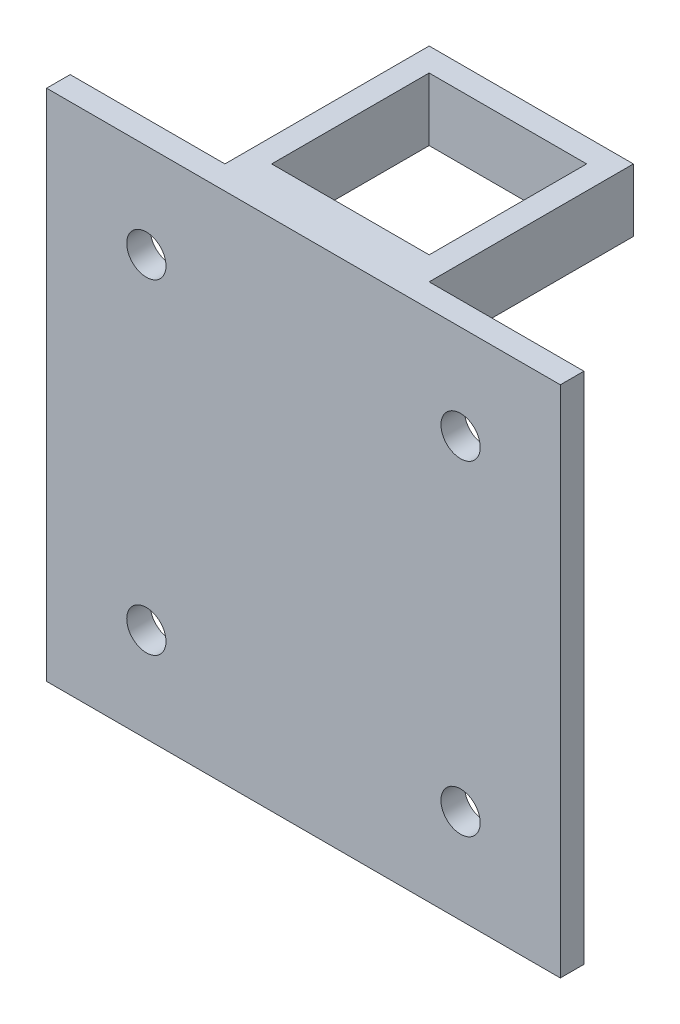
SolidWorks part; units mm, degrees
ref_plane "Спереди" through (0, 0, 0) normal (0, 0, 1) x (1, 0, 0)
ref_plane "Сверху" through (0, 0, 0) normal (0, 1, 0) x (1, 0, 0)
ref_plane "Справа" through (0, 0, 0) normal (1, 0, 0) x (0, 0, -1)
sketch "Эскиз1" plane through (0, 0, 0) normal (0, 0, 1) x (1, 0, 0)
  line L0 (-65.4, 53.4) -> (0, 53.4) construction
  line L1 (0, 0) -> (-65.4, 0)
  line L2 (0, 0) -> (0, 65.4)
  line L3 (0, 65.4) -> (-65.4, 65.4)
  line L4 (-65.4, 0) -> (-65.4, 65.4)
  line L5 (-32.7, 65.4) -> (-32.7, 0) construction
  line L6 (-65.4, 32.7) -> (0, 32.7) construction
  circle A0 centre (-52.7, 53.4) radius 2.5
  circle A2 centre (-12.7, 53.4) radius 2.5
  circle A3 centre (-12.7, 12) radius 2.5
  circle A4 centre (-52.7, 12) radius 2.5
  dimension "D4" = 5
  dimension "D5" = 20
  dimension "D1" = 65.4
  dimension "D2" = 65.4
  dimension "D3" = 12
extrude "каретка" add sketch "Эскиз1" along normal blind 3
sketch "Эскиз2" plane through (0, 0, 0) normal (0, 0, -1) x (-1, 0, 0)
  line L0 (0, 65.4) -> (65.4, 65.4) construction
  line L1 (19.7, 65.4) -> (45.7, 65.4)
  line L2 (19.7, 65.4) -> (19.7, 57.4)
  line L3 (19.7, 57.4) -> (45.7, 57.4)
  line L4 (45.7, 65.4) -> (45.7, 57.4)
  line L5 (32.7, 65.4) -> (32.7, 0) construction
  line L6 (65.4, 0) -> (0, 0) construction
  point P10 (32.7, 65.4)
  dimension "D1" = 8
  dimension "D2" = 26
extrude "крепеж для направляющей" add sketch "Эскиз2" along normal blind 26
sketch "Эскиз3" plane through (0, 57.4, 0) normal (0, -1, 0) x (1, 0, 0)
  line L0 (-45.7, -13) -> (-19.7, -13) construction
  line L1 (-42.725, -2.975) -> (-22.675, -2.975)
  line L2 (-42.725, -2.975) -> (-42.725, -23.025)
  line L3 (-42.725, -23.025) -> (-22.675, -23.025)
  line L4 (-22.675, -2.975) -> (-22.675, -23.025)
  line L5 (-45.7, -26) -> (-45.7, 0) construction
  line L6 (-19.7, -26) -> (-19.7, 0) construction
  line L7 (-42.725, -13) -> (-22.675, -13) construction
  point P12 (-32.7, -13)
  point P13 (-32.7, -13)
  dimension "D1" = 20.05
  dimension "D2" = 20.05
extrude "дырка в крепеже для направляющей" cut sketch "Эскиз3" against normal through all
sketch "Эскиз4" plane through (0, 0, 0) normal (0, 0, -1) x (-1, 0, 0)
  line L0 (12.7, 53.4) -> (12.7, 12) construction
  circle A0 centre (12.7, 32.7) radius 5
  circle A1 centre (12.7, 32.7) radius 2
  dimension "D1" = 4
  dimension "D2" = 10
extrude "для гладкого ролика" add sketch "Эскиз4" along normal blind 6.6
sketch "Эскиз5" plane through (0, 0, 0) normal (0, 0, -1) x (-1, 0, 0)
  line L0 (52.7, 53.4) -> (52.7, 12) construction
  circle A0 centre (52.7, 32.7) radius 2.4
  dimension "D1" = 4.8
extrude "Бобышка-Вытянуть1" add sketch "Эскиз5" along normal blind 16
